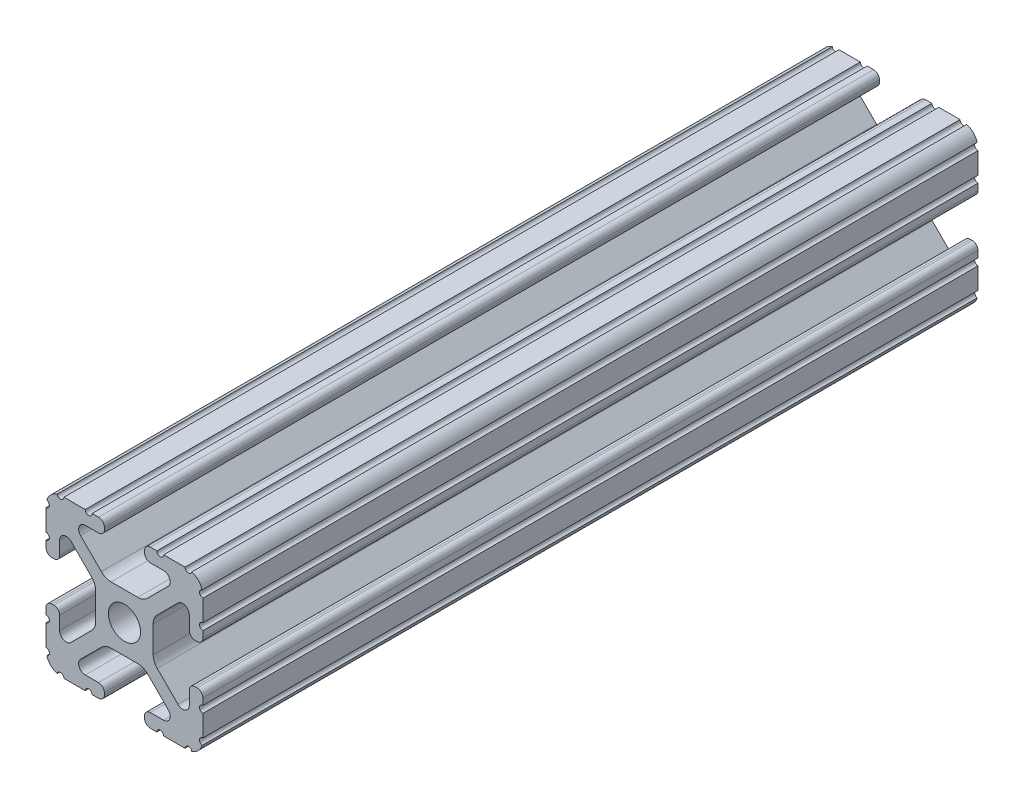
SolidWorks part; units mm, degrees
ref_plane "Front Plane" through (0, 0, 0) normal (0, 0, 1) x (1, 0, 0)
ref_plane "Top Plane" through (0, 0, 0) normal (0, 1, 0) x (1, 0, 0)
ref_plane "Right Plane" through (0, 0, 0) normal (1, 0, 0) x (0, 0, -1)
sketch "Sketch2" plane through (0, 0, 0) normal (0, 0, 1) x (1, 0, 0)
  line L0 (0, 12.7) -> (0, -12.7) construction
  line L1 (-12.7, 0) -> (12.7, 0) construction
  line L2 (3.2512, -12.7) -> (12.7, -12.7)
  line L3 (12.7, -12.7) -> (12.7, -3.2512)
  line L4 (3.2512, -12.7) -> (3.2512, -10.4902)
  line L5 (3.2512, -10.4902) -> (8.9276, -10.4902)
  line L6 (8.9276, -10.4902) -> (3.0856, -4.6482)
  line L7 (0, 0) -> (12.7, -12.7) construction
  line L8 (12.7, -3.2512) -> (10.4902, -3.2512)
  line L9 (10.4902, -3.2512) -> (10.4902, -8.9276)
  line L10 (10.4902, -8.9276) -> (4.6482, -3.0856)
  circle A0 centre (0, 0) radius 2.6035
  arc A1 (6.3485, -10.4902) -> (7.1039, -8.6665) centre (6.3485, -9.4219) ccw construction
  point P8 (0, -4.6482)
  dimension "Center Hole Diameter" = 5.207
  dimension "Rail Height" = 25.4
  dimension "Rail Width" = 25.4
  dimension "T-Slot Width" = 6.5024
  dimension "Slot Inner Width" = 14.8336
  dimension "Thickness" = 2.2098
  dimension "Slot Depth" = 5.842
  dimension "D1" = 2.2098
sketch "Sketch3" plane through (0, 0, 0) normal (1, 0, 0) x (0, 0, -1)
  line L0 (-76.2, -12.7) -> (76.2, -12.7) construction
  line L1 (-68.58, 0) -> (68.58, 0) construction
  dimension "Length" = 152.4
  dimension "D1" = 137.16
sketch "Sketch4" plane through (0, 0, 0) normal (0, 0, 1) x (1, 0, 0)
  line L0 (4.1904, -12.7) -> (10.1173, -12.7)
  line L1 (3.2512, -12.7) -> (12.7, -12.7) construction
  line L2 (3.2512, -12.7) -> (3.2512, -10.4902) construction
  line L3 (3.2512, -10.4902) -> (8.9276, -10.4902) construction
  line L4 (3.2512, -11.4294) -> (3.2512, -11.7608)
  line L5 (4.1904, -10.4902) -> (6.3485, -10.4902)
  line L6 (0, -4.6482) -> (2.164, -4.6482)
  line L7 (8.9276, -10.4902) -> (3.0856, -4.6482) construction
  line L8 (3.7373, -5.2999) -> (7.1039, -8.6665)
  line L9 (12.7, -12.7) -> (12.7, -3.2512) construction
  line L10 (10.4902, -8.9276) -> (4.6482, -3.0856) construction
  line L11 (10.4902, -3.2512) -> (10.4902, -8.9276) construction
  line L12 (10.4902, -6.3485) -> (10.4902, -4.1904)
  line L13 (12.7, -3.2512) -> (10.4902, -3.2512) construction
  line L14 (11.4294, -3.2512) -> (11.7608, -3.2512)
  line L15 (12.7, -4.1904) -> (12.7, -10.1173)
  line L16 (8.6665, -7.1039) -> (5.2999, -3.7373)
  line L17 (4.6482, 0) -> (4.6482, -2.164)
  line L18 (-12.7, 0) -> (12.7, 0) construction
  line L19 (0, -4.6482) -> (0, -2.6035)
  line L20 (0, 12.7) -> (0, -12.7) construction
  line L21 (4.6482, 0) -> (2.6035, 0)
  arc A0 (3.2512, -11.7608) -> (4.1904, -12.7) centre (4.1904, -11.7608) ccw
  arc A2 (3.2512, -11.4294) -> (4.1904, -10.4902) centre (4.1904, -11.4294) cw
  arc A3 (6.3485, -10.4902) -> (7.1039, -8.6665) centre (6.3485, -9.4219) ccw
  arc A4 (2.164, -4.6482) -> (3.7373, -5.2999) centre (2.164, -6.8732) cw
  arc A5 (10.1173, -12.7) -> (12.7, -10.1173) centre (10.1173, -10.1173) ccw
  arc A6 (8.6665, -7.1039) -> (10.4902, -6.3485) centre (9.4219, -6.3485) ccw
  arc A7 (10.4902, -4.1904) -> (11.4294, -3.2512) centre (11.4294, -4.1904) cw
  arc A8 (11.7608, -3.2512) -> (12.7, -4.1904) centre (11.7608, -4.1904) cw
  arc A9 (5.2999, -3.7373) -> (4.6482, -2.164) centre (6.8732, -2.164) cw
  circle A10 centre (0, 0) radius 2.6035 construction
  arc A11 (0, -2.6035) -> (2.6035, 0) centre (0, 0) ccw
  dimension "D1" = 2.5827
  dimension "D2" = 2.225
  dimension "D3" = 0.9392
extrude "Boss-Extrude1" add sketch "Sketch4" along normal mid plane 152.4
sketch "Sketch5" plane through (0, 0, 0) normal (0, 0, 1) x (1, 0, 0)
  line L0 (3.2512, -12.7) -> (12.7, -12.7) construction
  line L1 (4.1904, -10.4902) -> (6.3485, -10.4902) construction
  line L3 (0, 0) -> (12.7, -12.7) construction
  line L4 (6.3485, -10.4902) -> (6.3485, -12.7) construction
  line L5 (8.9276, -10.4902) -> (3.0856, -4.6482) construction
  circle A0 centre (10.3562, -12.7) radius 0.5524
  circle A1 centre (5.796, -12.7) radius 0.5524
  circle A2 centre (12.7, -10.3562) radius 0.5524
  circle A3 centre (12.7, -5.796) radius 0.5524
  point P10 (5.2694, -10.4902)
  point P12 (9.4219, -6.3485)
  dimension "D1" = 1.1049
extrude "Cut-Extrude1" cut sketch "Sketch5" against normal through all both and the other way through all
mirror "Mirror1" about plane through (0, 0, 0) normal (1, 0, 0) of bodies 137 134
mirror "Mirror2" about plane through (0, 0, 0) normal (0, 1, 0) of bodies 135
sketch "Sketch6" plane through (0, 0, 76.2) normal (0, 0, 1) x (1, 0, 0)
  line L1 (-15.24, -15.24) -> (15.24, -15.24)
  line L2 (-15.24, -15.24) -> (-15.24, 15.24)
  line L3 (-15.24, 15.24) -> (15.24, 15.24)
  line L4 (15.24, -15.24) -> (15.24, 15.24)
  line L5 (-15.24, -15.24) -> (15.24, 15.24) construction
  line L6 (-15.24, 15.24) -> (15.24, -15.24) construction
  point P0 (0, 0)
  dimension "D1" = 30.48
  dimension "D2" = 30.48
extrude "Cut-Extrude2" cut sketch "Sketch6" against normal blind 26.924
equation "\"D1@Boss-Extrude1\"=\"Length@Sketch3\""
equation "\"D1@Sketch2\"=\"Thickness@Sketch2\""
equation "\"D2@Sketch4\"=\"Slot Inner Width@Sketch2\"*0.15"
equation "\"D1@Sketch4\"=\"D3@Sketch4\"*2.75"
equation "\"D3@Sketch4\"=\"Thickness@Sketch2\"*0.425"
equation "\"D1@Sketch5\"=\"Thickness@Sketch2\"*0.5"
equation "\"D1@Sketch3\"=\"Length@Sketch3\"*0.9"
